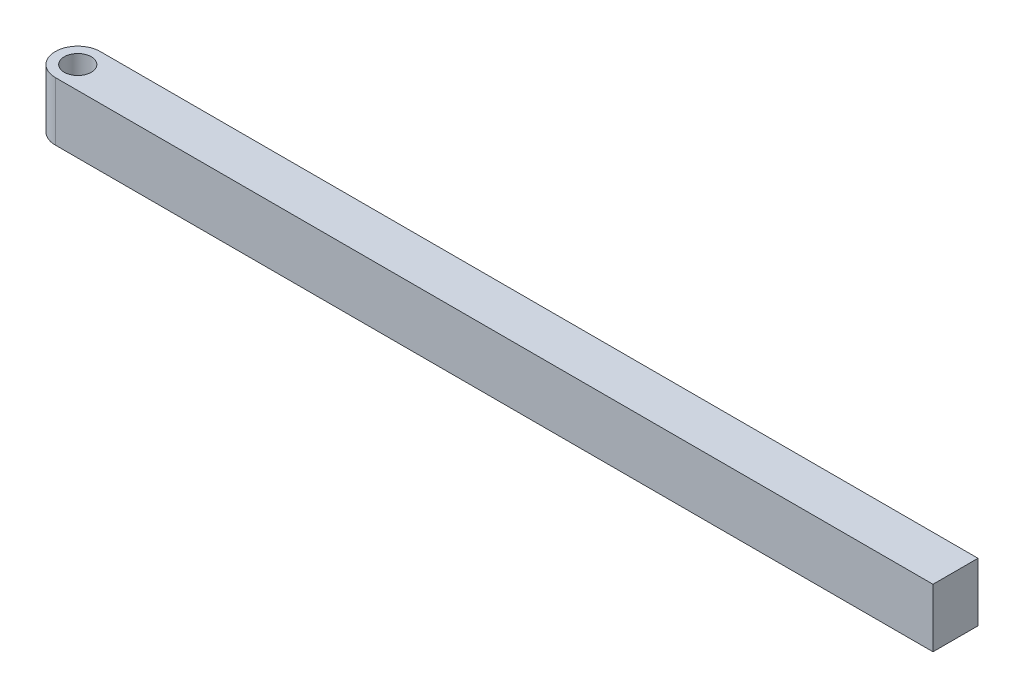
SolidWorks part; units mm, degrees
ref_plane "Front Plane" through (0, 0, 0) normal (1, 0, 0) x (0, 1, 0)
ref_plane "Top Plane" through (0, 0, 0) normal (0, 0, 1) x (0, 1, 0)
ref_plane "Right Plane" through (0, 0, 0) normal (0, 1, 0) x (-1, 0, 0)
sketch "Sketch1" plane through (0, 0, 0) normal (1, 0, 0) x (0, 1, 0)
  line L1 (-6.5, -5) -> (6.5, -5)
  line L2 (-6.5, -5) -> (-6.5, 5)
  line L3 (-6.5, 5) -> (6.5, 5)
  line L4 (6.5, -5) -> (6.5, 5)
  line L5 (0, 5) -> (0, -5) construction
  line L6 (-6.5, 0) -> (6.5, 0) construction
  point P0 (0, 0)
  dimension "D1" = 10
  dimension "D2" = 13
extrude "Boss-Extrude1" add sketch "Sketch1" along normal blind 200
sketch "Sketch2" plane through (0, 6.5, 0) normal (0, 1, 0) x (-1, 0, 0)
  line L0 (0, -5) -> (0, 5) construction
  circle A0 centre (-5, 0) radius 3
  dimension "D1" = 6
  dimension "D2" = 5
extrude "Cut-Extrude1" cut sketch "Sketch2" against normal through all contours A0
fillet "Fillet1" radius 5 2 edges at (0, 0, 5) (0, 0, -5)
